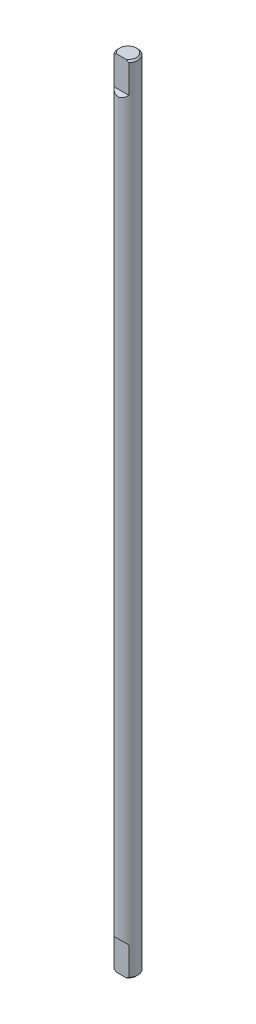
SolidWorks part; units mm, degrees
ref_plane "Ebene vorne" through (0, 0, 0) normal (0, 0, 1) x (1, 0, 0)
ref_plane "Ebene oben" through (0, 0, 0) normal (0, 1, 0) x (1, 0, 0)
ref_plane "Ebene rechts" through (0, 0, 0) normal (1, 0, 0) x (0, 0, -1)
sketch "Skizze1" plane through (0, 0, 0) normal (0, 1, 0) x (1, 0, 0)
  circle A0 centre (0, 0) radius 3
  dimension "D1" = 6
extrude "Aufsatz-Linear austragen1" add sketch "Skizze1" along normal blind 240
chamfer "Fase2" distance 0.5 angle 45 2 edges at (0, 240, 3) (0, 0, 3)
sketch "Skizze2" plane through (0, 0, 0) normal (0, 0, 1) x (1, 0, 0)
  line L0 (3, 120) -> (-3, 120) construction
  line L1 (3, 0.5) -> (3, 239.5) construction
  line L2 (-3, 239.5) -> (-3, 0.5) construction
  line L3 (3, 240) -> (3, 230)
  line L4 (-3, 0) -> (3, 0)
  line L5 (-3, 0) -> (-3, 10)
  line L6 (-3, 10) -> (3, 10)
  line L7 (3, 0) -> (3, 10)
  line L8 (-3, 230) -> (3, 230)
  line L9 (-3, 240) -> (-3, 230)
  line L10 (-3, 240) -> (3, 240)
  point P15 (0, 0)
  dimension "D1" = 10
  dimension "D2" = 0
extrude "Schnitt-Linear austragen1" cut sketch "Skizze2" along normal through all from offset 2
chamfer "Fase1" distance 1 angle 45 2 edges at (0, 230, 2) (0, 10, 2)
